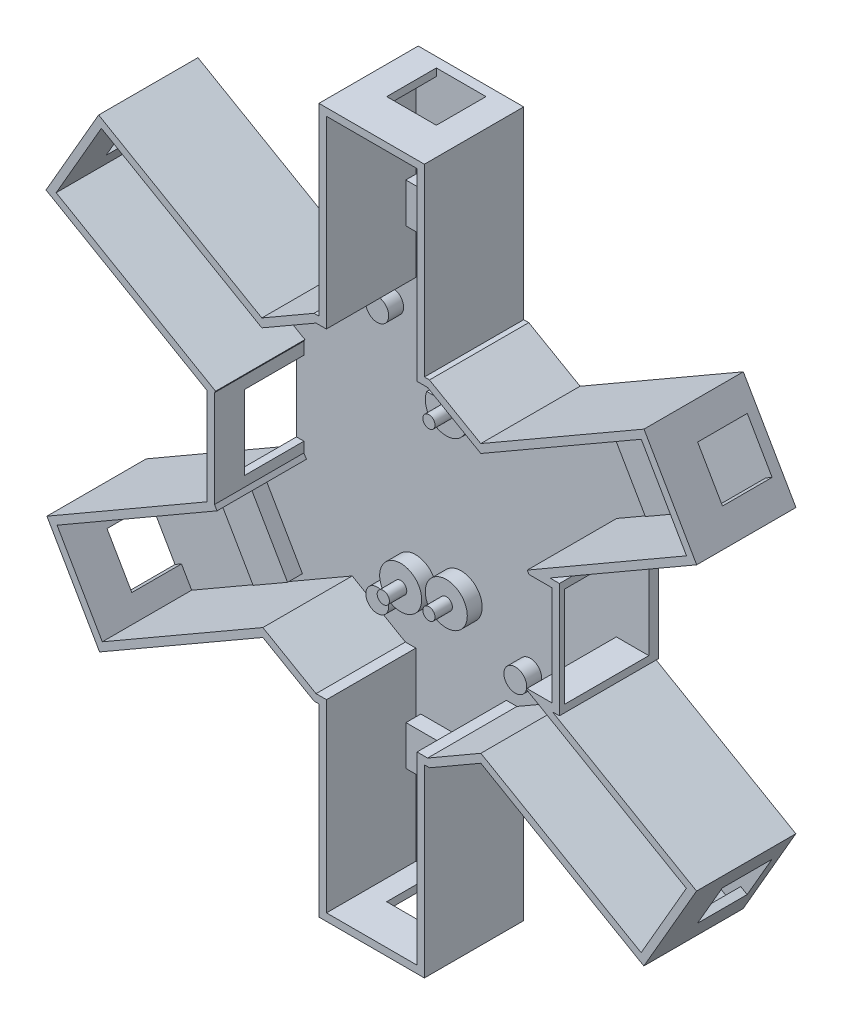
SolidWorks part; units mm, degrees
ref_plane "Ebene vorne" through (0, 0, 0) normal (0, 0, 1) x (1, 0, 0)
ref_plane "Ebene oben" through (0, 0, 0) normal (0, 1, 0) x (1, 0, 0)
ref_plane "Ebene rechts" through (0, 0, 0) normal (1, 0, 0) x (0, 0, -1)
sketch "Skizze1" plane through (0, 0, 0) normal (0, 0, 1) x (1, 0, 0)
  line L0 (-22.15, 25.11) -> (-11.02, 31.53) construction
  line L1 (-11.02, 31.53) -> (-8.35, 31.53) construction
  line L2 (-8.35, 31.53) -> (-8.35, 68.65) construction
  line L3 (-8.35, 68.65) -> (8.29, 68.65) construction
  line L4 (8.29, 68.65) -> (8.29, 31.53) construction
  line L5 (8.29, 31.53) -> (11, 31.53) construction
  line L6 (11, 31.53) -> (21.95, 25.25) construction
  line L7 (21.95, 25.25) -> (53.98, 43.72) construction
  line L8 (53.98, 43.72) -> (62.29, 29.33) construction
  line L9 (-62.48, 29.19) -> (-54.18, 43.59) construction
  line L10 (-54.18, 43.59) -> (-22.15, 25.11) construction
  line L11 (-30.38, 10.62) -> (-62.48, 29.19) construction
  line L12 (-30.88, 9.75) -> (-30.38, 10.62) construction
  line L13 (-30.88, -9.32) -> (-30.88, 9.75) construction
  line L14 (-30.05, -10.67) -> (-30.88, -9.32) construction
  line L15 (-62.3, -29.3) -> (-30.05, -10.67) construction
  line L16 (-53.99, -43.7) -> (-62.3, -29.3) construction
  line L17 (-21.73, -25.09) -> (-53.99, -43.7) construction
  line L18 (-21.52, -25.46) -> (-21.73, -25.09) construction
  line L19 (-11.02, -31.51) -> (-21.52, -25.46) construction
  line L20 (-8.33, -31.51) -> (-11.02, -31.51) construction
  line L21 (-8.33, -68.7) -> (-8.33, -31.51) construction
  line L22 (8.29, -68.7) -> (-8.33, -68.7) construction
  line L23 (8.31, -31.51) -> (8.29, -68.7) construction
  line L24 (11.02, -31.51) -> (8.31, -31.51) construction
  line L25 (21.5, -25.46) -> (11.02, -31.51) construction
  line L26 (21.73, -25.06) -> (21.5, -25.46) construction
  line L27 (53.95, -43.66) -> (21.73, -25.06) construction
  line L28 (62.26, -29.27) -> (53.95, -43.66) construction
  line L29 (30.04, -10.67) -> (62.26, -29.27) construction
  line L30 (30.79, -9.37) -> (30.04, -10.67) construction
  line L31 (35.49, -9.37) -> (30.79, -9.37) construction
  line L32 (35.49, 9.12) -> (35.49, -9.37) construction
  line L33 (31.19, 9.12) -> (35.49, 9.12) construction
  line L34 (30.22, 10.81) -> (31.19, 9.12) construction
  line L35 (62.29, 29.33) -> (30.22, 10.81) construction
  line L36 (-22.15, 25.11) -> (-11.02, 31.53) construction
  line L37 (-11.02, 31.53) -> (-8.35, 31.53) construction
  line L38 (-8.35, 31.53) -> (-8.35, 68.65) construction
  line L39 (-8.35, 68.65) -> (8.29, 68.65) construction
  line L40 (8.29, 68.65) -> (8.29, 31.53) construction
  line L41 (8.29, 31.53) -> (11, 31.53) construction
  line L42 (11, 31.53) -> (21.95, 25.25) construction
  line L43 (21.95, 25.25) -> (53.98, 43.72) construction
  line L44 (53.98, 43.72) -> (62.29, 29.33) construction
  line L45 (-62.48, 29.19) -> (-54.18, 43.59) construction
  line L46 (-54.18, 43.59) -> (-22.15, 25.11) construction
  line L47 (-30.38, 10.62) -> (-62.48, 29.19) construction
  line L48 (-30.88, 9.75) -> (-30.38, 10.62) construction
  line L49 (-30.88, -9.32) -> (-30.88, 9.75) construction
  line L50 (-30.05, -10.67) -> (-30.88, -9.32) construction
  line L51 (-62.3, -29.3) -> (-30.05, -10.67) construction
  line L52 (-53.99, -43.7) -> (-62.3, -29.3) construction
  line L53 (-21.73, -25.09) -> (-53.99, -43.7) construction
  line L54 (-21.52, -25.46) -> (-21.73, -25.09) construction
  line L55 (-11.02, -31.51) -> (-21.52, -25.46) construction
  line L56 (-8.33, -31.51) -> (-11.02, -31.51) construction
  line L57 (-8.33, -68.7) -> (-8.33, -31.51) construction
  line L58 (8.29, -68.7) -> (-8.33, -68.7) construction
  line L59 (8.31, -31.51) -> (8.29, -68.7) construction
  line L60 (11.02, -31.51) -> (8.31, -31.51) construction
  line L61 (21.5, -25.46) -> (11.02, -31.51) construction
  line L62 (21.73, -25.06) -> (21.5, -25.46) construction
  line L63 (53.95, -43.66) -> (21.73, -25.06) construction
  line L64 (62.26, -29.27) -> (53.95, -43.66) construction
  line L65 (30.04, -10.67) -> (62.26, -29.27) construction
  line L66 (30.79, -9.37) -> (30.04, -10.67) construction
  line L67 (35.49, -9.37) -> (30.79, -9.37) construction
  line L68 (35.49, 9.12) -> (35.49, -9.37) construction
  line L69 (31.19, 9.12) -> (35.49, 9.12) construction
  line L70 (30.22, 10.81) -> (31.19, 9.12) construction
  line L71 (62.29, 29.33) -> (30.22, 10.81) construction
  line L72 (-22.15, 26.0336) -> (-11.2342, 32.33)
  line L73 (-11.2342, 32.33) -> (-9.15, 32.33)
  line L74 (-9.15, 32.33) -> (-9.15, 69.45)
  line L75 (-9.15, 69.45) -> (9.09, 69.45)
  line L76 (9.09, 69.45) -> (9.09, 32.33)
  line L77 (9.09, 32.33) -> (11.2131, 32.33)
  line L78 (11.2131, 32.33) -> (21.9489, 26.1729)
  line L79 (21.9489, 26.1729) -> (54.273, 44.8124)
  line L80 (54.273, 44.8124) -> (63.3828, 29.0373)
  line L81 (63.3828, 29.0373) -> (31.311, 10.5162)
  line L82 (31.311, 10.5162) -> (31.6532, 9.92)
  line L83 (31.6532, 9.92) -> (36.29, 9.92)
  line L84 (36.29, 9.92) -> (36.29, -10.17)
  line L85 (36.29, -10.17) -> (31.2521, -10.17)
  line L86 (31.2521, -10.17) -> (31.1326, -10.377)
  line L87 (31.1326, -10.377) -> (63.3529, -28.9772)
  line L88 (63.3529, -28.9772) -> (54.2428, -44.7527)
  line L89 (54.2428, -44.7527) -> (21.9615, -26.1173)
  line L90 (21.9615, -26.1173) -> (21.9615, -26.1173)
  line L91 (21.9615, -26.1173) -> (11.2343, -32.31)
  line L92 (11.2343, -32.31) -> (9.1096, -32.31)
  line L93 (9.1096, -32.31) -> (9.0896, -69.5)
  line L94 (9.0896, -69.5) -> (-9.13, -69.5)
  line L95 (-9.13, -69.5) -> (-9.13, -32.31)
  line L96 (-9.13, -32.31) -> (-11.234, -32.31)
  line L97 (-11.234, -32.31) -> (-21.9457, -26.138)
  line L98 (-21.9457, -26.138) -> (-21.9457, -26.138)
  line L99 (-21.9457, -26.138) -> (-54.2831, -44.7927)
  line L100 (-54.2831, -44.7927) -> (-63.3926, -29.0073)
  line L101 (-63.3926, -29.0073) -> (-31.1621, -10.3886)
  line L102 (-31.1621, -10.3886) -> (-31.68, -9.5463)
  line L103 (-31.68, -9.5463) -> (-31.68, 9.9635)
  line L104 (-31.68, 9.9635) -> (-31.4711, 10.327)
  line L105 (-31.4711, 10.327) -> (-63.572, 28.8975)
  line L106 (-63.572, 28.8975) -> (-54.4734, 44.6829)
  line L107 (-54.4734, 44.6829) -> (-22.15, 26.0336)
  line L108 (-22.1499, 27.7653) -> (-11.6358, 33.83)
  line L109 (-11.6358, 33.83) -> (-10.65, 33.83)
  line L110 (-10.65, 33.83) -> (-10.65, 70.95)
  line L111 (-10.65, 70.95) -> (10.59, 70.95)
  line L112 (10.59, 70.95) -> (10.59, 33.83)
  line L113 (10.59, 33.83) -> (11.6127, 33.83)
  line L114 (11.6127, 33.83) -> (21.9469, 27.9032)
  line L115 (21.9469, 27.9032) -> (54.8223, 46.8607)
  line L116 (54.8223, 46.8607) -> (65.4319, 28.4885)
  line L117 (65.4319, 28.4885) -> (35.8755, 11.42)
  line L118 (35.8755, 11.42) -> (35.8755, 11.42)
  line L119 (35.8755, 11.42) -> (37.79, 11.42)
  line L120 (37.79, 11.42) -> (37.79, -11.67)
  line L121 (37.79, -11.67) -> (36.3727, -11.67)
  line L122 (36.3727, -11.67) -> (36.3727, -11.67)
  line L123 (36.3727, -11.67) -> (65.4021, -28.4282)
  line L124 (65.4021, -28.4282) -> (54.7917, -46.8016)
  line L125 (54.7917, -46.8016) -> (21.9615, -27.8493)
  line L126 (21.9615, -27.8493) -> (21.9615, -27.8493)
  line L127 (21.9615, -27.8493) -> (11.6362, -33.81)
  line L128 (11.6362, -33.81) -> (10.6088, -33.81)
  line L129 (10.6088, -33.81) -> (10.5888, -71)
  line L130 (10.5888, -71) -> (-10.63, -71)
  line L131 (-10.63, -71) -> (-10.63, -33.81)
  line L132 (-10.63, -33.81) -> (-11.6352, -33.81)
  line L133 (-11.6352, -33.81) -> (-21.9453, -27.8694)
  line L134 (-21.9453, -27.8694) -> (-21.9453, -27.8694)
  line L135 (-21.9453, -27.8694) -> (-54.8327, -46.8414)
  line L136 (-54.8327, -46.8414) -> (-65.4412, -28.4584)
  line L137 (-65.4412, -28.4584) -> (-33.18, -9.8219)
  line L138 (-33.18, -9.8219) -> (-33.18, -9.8219)
  line L139 (-33.18, -9.8219) -> (-33.18, 9.5827)
  line L140 (-33.18, 9.5827) -> (-33.18, 9.5827)
  line L141 (-33.18, 9.5827) -> (-65.6194, 28.349)
  line L142 (-65.6194, 28.349) -> (-55.0236, 46.7321)
  line L143 (-55.0236, 46.7321) -> (-22.1499, 27.7653)
  dimension "D1" = 0.8
  dimension "D2" = 1.5
extrude "Aufsatz-Linear austragen1" add sketch "Skizze1" along normal blind 18
sketch "Skizze3" plane through (0, 0, 0) normal (0, 0, -1) x (-1, 0, 0)
  line L31 (55.0236, 46.7321) -> (22.1499, 27.7653)
  line L32 (22.1499, 27.7653) -> (11.6358, 33.83)
  line L33 (11.6358, 33.83) -> (10.65, 33.83)
  line L34 (10.65, 33.83) -> (10.65, 70.95)
  line L35 (10.65, 70.95) -> (-10.59, 70.95)
  line L36 (-10.59, 70.95) -> (-10.59, 33.83)
  line L37 (-10.59, 33.83) -> (-11.6127, 33.83)
  line L38 (-11.6127, 33.83) -> (-21.9469, 27.9032)
  line L39 (-21.9469, 27.9032) -> (-54.8223, 46.8607)
  line L40 (-54.8223, 46.8607) -> (-65.4319, 28.4885)
  line L41 (-65.4319, 28.4885) -> (-35.8755, 11.42)
  line L42 (-35.8755, 11.42) -> (-37.79, 11.42)
  line L43 (-37.79, 11.42) -> (-37.79, -11.67)
  line L44 (-37.79, -11.67) -> (-36.3727, -11.67)
  line L45 (-36.3727, -11.67) -> (-65.4021, -28.4282)
  line L46 (-65.4021, -28.4282) -> (-54.7917, -46.8016)
  line L47 (-54.7917, -46.8016) -> (-21.9615, -27.8493)
  line L48 (-21.9615, -27.8493) -> (-11.6362, -33.81)
  line L49 (-11.6362, -33.81) -> (-10.6088, -33.81)
  line L50 (-10.6088, -33.81) -> (-10.5888, -71)
  line L51 (-10.5888, -71) -> (10.63, -71)
  line L52 (10.63, -71) -> (10.63, -33.81)
  line L53 (10.63, -33.81) -> (11.6352, -33.81)
  line L54 (11.6352, -33.81) -> (21.9453, -27.8694)
  line L55 (21.9453, -27.8694) -> (54.8327, -46.8414)
  line L56 (54.8327, -46.8414) -> (65.4412, -28.4584)
  line L57 (65.4412, -28.4584) -> (33.18, -9.8219)
  line L59 (33.18, -9.8219) -> (33.18, 9.5827)
  line L60 (33.18, 9.5827) -> (65.6194, 28.349)
  line L61 (65.6194, 28.349) -> (55.0236, 46.7321)
  line L62 (55.0236, 46.7321) -> (22.1499, 27.7653)
  line L63 (22.1499, 27.7653) -> (11.6358, 33.83)
  line L64 (11.6358, 33.83) -> (10.65, 33.83)
  line L65 (10.65, 33.83) -> (10.65, 70.95)
  line L66 (10.65, 70.95) -> (-10.59, 70.95)
  line L67 (-10.59, 70.95) -> (-10.59, 33.83)
  line L68 (-10.59, 33.83) -> (-11.6127, 33.83)
  line L69 (-11.6127, 33.83) -> (-21.9469, 27.9032)
  line L70 (-21.9469, 27.9032) -> (-54.8223, 46.8607)
  line L71 (-54.8223, 46.8607) -> (-65.4319, 28.4885)
  line L72 (-65.4319, 28.4885) -> (-35.8755, 11.42)
  line L73 (-35.8755, 11.42) -> (-37.79, 11.42)
  line L74 (-37.79, 11.42) -> (-37.79, -11.67)
  line L75 (-37.79, -11.67) -> (-36.3727, -11.67)
  line L76 (-36.3727, -11.67) -> (-65.4021, -28.4282)
  line L77 (-65.4021, -28.4282) -> (-54.7917, -46.8016)
  line L78 (-54.7917, -46.8016) -> (-21.9615, -27.8493)
  line L79 (-21.9615, -27.8493) -> (-11.6362, -33.81)
  line L80 (-11.6362, -33.81) -> (-10.6088, -33.81)
  line L81 (-10.6088, -33.81) -> (-10.5888, -71)
  line L82 (-10.5888, -71) -> (10.63, -71)
  line L83 (10.63, -71) -> (10.63, -33.81)
  line L84 (10.63, -33.81) -> (11.6352, -33.81)
  line L85 (11.6352, -33.81) -> (21.9453, -27.8694)
  line L86 (21.9453, -27.8694) -> (54.8327, -46.8414)
  line L87 (54.8327, -46.8414) -> (65.4412, -28.4584)
  line L88 (65.4412, -28.4584) -> (33.18, -9.8219)
  line L90 (33.18, -9.8219) -> (33.18, 9.5827)
  line L91 (33.18, 9.5827) -> (65.6194, 28.349)
  line L92 (65.6194, 28.349) -> (55.0236, 46.7321)
  dimension "D1" = 0
extrude "Aufsatz-Linear austragen2" add sketch "Skizze3" along normal blind 2
sketch "Skizze4" plane through (36.29, 0, 0) normal (-1, 0, 0) x (0, 0, 1)
  line L0 (17.0038, 9.92) -> (17.0038, -10.17)
  line L1 (0.8513, 9.92) -> (0, 9.92)
  line L2 (17.0038, -10.17) -> (0.8513, -10.17)
  line L3 (17.0038, 9.92) -> (0.8513, 9.92)
  line L4 (0, 9.92) -> (0, -10.17)
  line L5 (0, -10.17) -> (18, -10.17)
  line L6 (18, -10.17) -> (18, 9.92)
  line L7 (18, 9.92) -> (0, 9.92)
  line L8 (0, 9.92) -> (0, -10.17) construction
  line L9 (0, -10.17) -> (18, -10.17) construction
  line L10 (18, -10.17) -> (18, 9.92) construction
  line L11 (18, 9.92) -> (0, 9.92) construction
  line L12 (0, 9.92) -> (0, -10.17)
  line L13 (0, -10.17) -> (0.8513, -10.17)
  dimension "D1" = 0
extrude "Schnitt-Linear austragen1" cut sketch "Skizze4" against normal up to next
sketch "Skizze5" plane through (-31.68, 0, 0) normal (1, 0, 0) x (0, 0, -1)
  line L0 (-12, -7.5) -> (-12, 7.5)
  line L1 (-12, -7.5) -> (0, -7.5)
  line L2 (-12, 7.5) -> (0, 7.5)
  line L3 (0, -7.5) -> (0, 7.5)
  line L4 (-12, -7.5) -> (0, 7.5) construction
  line L5 (-12, 7.5) -> (0, -7.5) construction
  line L6 (0, 9.9635) -> (0, -9.5463) construction
  point P1 (-6, 0)
  dimension "D1" = 15
  dimension "D2" = 12
  dimension "D3" = 0
extrude "Schnitt-Linear austragen2" cut sketch "Skizze5" against normal up to next
sketch "Skizze6" plane through (0, -71, 0) normal (0, -1, 0) x (1, 0, 0)
  line L0 (-9.13, 0) -> (9.0896, 0) construction
  line L1 (5, 10) -> (-5, 10)
  line L2 (5, 10) -> (5, 0)
  line L3 (5, 0) -> (-5, 0)
  line L4 (-5, 10) -> (-5, 0)
  line L5 (5, 10) -> (-5, 0) construction
  line L6 (5, 0) -> (-5, 10) construction
  line L7 (-9.13, 0) -> (9.0896, 0) construction
  point P0 (0, 5)
  dimension "D1" = 10
  dimension "D2" = 10
sketch "Skizze7" plane through (0, 0, 0) normal (0, 0, 1) x (1, 0, 0)
  circle A0 centre (-9.19, -20.27) radius 1.35 construction
  circle A1 centre (0, -18.5) radius 1.35 construction
  circle A2 centre (0, 15) radius 1.35 construction
  circle A3 centre (-9.19, -20.27) radius 4.35
  circle A4 centre (0, -18.5) radius 4.35
  circle A5 centre (0, 15) radius 4.35
  circle A6 centre (0, 15) radius 1.23
  circle A7 centre (0, -18.5) radius 1.23
  circle A8 centre (-9.19, -20.27) radius 1.23
  point P0 (-9.19, -21.62)
  point P1 (-7.84, -20.27)
  point P2 (-9.19, -18.92)
  point P3 (0, -17.15)
  point P5 (-1.35, -18.5)
  point P6 (0, -19.85)
  point P7 (-1.35, 15)
  point P8 (0, 16.35)
  point P13 (1.35, 15)
  dimension "D1" = 3
  dimension "D2" = 0.12
  dimension "D3" = 0.12
  dimension "D4" = 0.12
extrude "Aufsatz-Linear austragen3" add sketch "Skizze7" along normal blind 6.5 contours A6 | A7 | A8
sketch "Skizze8" plane through (0, 0, 0) normal (0, 0, 1) x (1, 0, 0)
  line L0 (3.9365, 16.5483) -> (-3.9365, 16.5483)
  circle A0 centre (-9.19, -20.27) radius 1.23 construction
  circle A1 centre (-9.19, -20.27) radius 1.23 construction
  circle A2 centre (0, -18.5) radius 1.23 construction
  circle A3 centre (0, -18.5) radius 1.23 construction
  circle A4 centre (0, 15) radius 1.23 construction
  circle A5 centre (0, 15) radius 1.23 construction
  circle A6 centre (-9.19, -20.27) radius 4.23
  circle A7 centre (0, -18.5) radius 4.23
  arc A8 (-3.9365, 16.5483) -> (3.9365, 16.5483) centre (0, 15) ccw
  circle A9 centre (0, 15) radius 4.23 construction
  circle A10 centre (13.9, 25.8971) radius 2.3
  circle A11 centre (-13.9, 25.8971) radius 2.3
  circle A12 centre (13.9, -24.8616) radius 2.3
  circle A13 centre (-13.9, -24.8616) radius 2.3
  dimension "D2" = 4.6
  dimension "D3" = 4.6
  dimension "D4" = 4.6
  dimension "D5" = 4.6
  dimension "D6" = 13.9
  dimension "D7" = 13.9
  dimension "D1" = 3
extrude "Aufsatz-Linear austragen4" add sketch "Skizze8" along normal blind 3
sketch "Skizze9" plane through (0, 0, 0) normal (0, 0, 1) x (1, 0, 0)
  line L0 (-9.13, -42.31) -> (-9.13, -52.31) construction
  line L1 (-9.13, -42.31) -> (9.0954, -42.31) construction
  line L2 (-9.13, -52.31) -> (9.0954, -52.31) construction
  line L3 (9.0954, -42.31) -> (9.0954, -52.31) construction
  line L4 (30.622, -31.1169) -> (39.2825, -36.1164) construction
  line L5 (30.622, -31.1169) -> (39.7347, -15.3313) construction
  line L6 (39.2825, -36.1164) -> (48.3952, -20.3309) construction
  line L7 (39.7347, -15.3313) -> (48.3952, -20.3309) construction
  line L8 (39.7303, 15.3783) -> (48.3901, 20.3792) construction
  line L9 (39.7303, 15.3783) -> (30.62, 31.1541) construction
  line L10 (48.3901, 20.3792) -> (39.2797, 36.155) construction
  line L11 (30.62, 31.1541) -> (39.2797, 36.155) construction
  line L12 (9.09, 42.33) -> (9.09, 52.33) construction
  line L13 (9.09, 42.33) -> (-9.1623, 42.33) construction
  line L14 (9.09, 52.33) -> (-9.1623, 52.33) construction
  line L15 (-9.1623, 42.33) -> (-9.1623, 52.33) construction
  line L16 (-39.4734, 36.0285) -> (-30.8117, 31.031) construction
  line L17 (-39.4734, 36.0285) -> (-48.6218, 20.1723) construction
  line L18 (-30.8117, 31.031) -> (-39.9601, 15.1748) construction
  line L19 (-48.6218, 20.1723) -> (-39.9601, 15.1748) construction
  line L20 (-48.3915, -20.3415) -> (-39.7324, -15.3394) construction
  line L21 (-48.3915, -20.3415) -> (-39.2717, -36.1285) construction
  line L22 (-39.7324, -15.3394) -> (-30.6127, -31.1264) construction
  line L23 (-39.2717, -36.1285) -> (-30.6127, -31.1264) construction
  line L24 (-39.107, 34.6626) -> (-47.2559, 20.5387)
  line L25 (-47.2559, 20.5387) -> (-40.3265, 16.5407)
  line L26 (-32.1776, 30.6646) -> (-40.3265, 16.5407)
  line L27 (-39.107, 34.6626) -> (-32.1776, 30.6646)
  line L28 (-8.1623, 43.33) -> (-8.1623, 51.33)
  line L29 (8.09, 51.33) -> (-8.1623, 51.33)
  line L30 (8.09, 43.33) -> (8.09, 51.33)
  line L31 (8.09, 43.33) -> (-8.1623, 43.33)
  line L32 (40.0962, 16.7443) -> (31.9861, 30.7882)
  line L33 (31.9861, 30.7882) -> (38.9139, 34.7889)
  line L34 (47.024, 20.745) -> (38.9139, 34.7889)
  line L35 (40.0962, 16.7443) -> (47.024, 20.745)
  line L36 (40.1008, -16.6973) -> (47.0292, -20.6969)
  line L37 (38.9164, -34.7504) -> (47.0292, -20.6969)
  line L38 (31.988, -30.7508) -> (38.9164, -34.7504)
  line L39 (31.988, -30.7508) -> (40.1008, -16.6973)
  line L40 (8.0954, -43.31) -> (8.0954, -51.31)
  line L41 (-8.13, -51.31) -> (8.0954, -51.31)
  line L42 (-8.13, -43.31) -> (-8.13, -51.31)
  line L43 (-8.13, -43.31) -> (8.0954, -43.31)
  line L44 (-38.906, -34.7624) -> (-31.9788, -30.7607)
  line L45 (-40.0981, -16.7055) -> (-31.9788, -30.7607)
  line L46 (-47.0253, -20.7072) -> (-40.0981, -16.7055)
  line L47 (-47.0253, -20.7072) -> (-38.906, -34.7624)
  line L50 (-11.2342, 32.33) -> (-22.15, 26.0336)
  line L51 (-22.15, 26.0336) -> (-54.4734, 44.6829)
  line L52 (-54.4734, 44.6829) -> (-63.572, 28.8975)
  line L53 (-63.572, 28.8975) -> (-31.4711, 10.327)
  line L54 (-31.4711, 10.327) -> (-31.68, 9.9635)
  line L55 (-31.68, 9.9635) -> (-31.68, 7.5)
  line L56 (-31.68, 7.5) -> (-33.18, 7.5)
  line L57 (-33.18, 7.5) -> (-33.18, -7.5)
  line L58 (-33.18, -7.5) -> (-31.68, -7.5)
  line L59 (-31.68, -7.5) -> (-31.68, -9.5463)
  line L60 (-31.68, -9.5463) -> (-31.1621, -10.3886)
  line L61 (-31.1621, -10.3886) -> (-63.3926, -29.0073)
  line L62 (-63.3926, -29.0073) -> (-54.2831, -44.7927)
  line L63 (-54.2831, -44.7927) -> (-21.9457, -26.138)
  line L64 (-21.9457, -26.138) -> (-11.234, -32.31)
  line L65 (-11.234, -32.31) -> (-9.13, -32.31)
  line L66 (-9.13, -32.31) -> (-9.13, -69.5)
  line L67 (-9.13, -69.5) -> (9.0896, -69.5)
  line L68 (9.0896, -69.5) -> (9.1096, -32.31)
  line L69 (9.1096, -32.31) -> (11.2343, -32.31)
  line L70 (11.2343, -32.31) -> (21.9615, -26.1173)
  line L71 (21.9615, -26.1173) -> (54.2428, -44.7527)
  line L72 (54.2428, -44.7527) -> (63.3529, -28.9772)
  line L73 (63.3529, -28.9772) -> (31.1326, -10.377)
  line L74 (31.1326, -10.377) -> (31.2521, -10.17)
  line L75 (31.2521, -10.17) -> (37.79, -10.17)
  line L76 (37.79, -10.17) -> (37.79, 9.92)
  line L77 (37.79, 9.92) -> (31.6532, 9.92)
  line L78 (31.6532, 9.92) -> (31.311, 10.5162)
  line L79 (31.311, 10.5162) -> (63.3828, 29.0373)
  line L80 (63.3828, 29.0373) -> (54.273, 44.8124)
  line L81 (54.273, 44.8124) -> (21.9489, 26.1729)
  line L82 (21.9489, 26.1729) -> (11.2131, 32.33)
  line L83 (11.2131, 32.33) -> (9.09, 32.33)
  line L84 (9.09, 32.33) -> (9.09, 69.45)
  line L85 (9.09, 69.45) -> (-9.15, 69.45)
  line L86 (-9.15, 69.45) -> (-9.15, 32.33)
  line L87 (-9.15, 32.33) -> (-11.2342, 32.33)
  line L88 (-11.2342, 32.33) -> (-22.15, 26.0336) construction
  line L89 (-22.15, 26.0336) -> (-54.4734, 44.6829) construction
  line L90 (-54.4734, 44.6829) -> (-63.572, 28.8975) construction
  line L91 (-63.572, 28.8975) -> (-31.4711, 10.327) construction
  line L92 (-31.4711, 10.327) -> (-31.68, 9.9635) construction
  line L93 (-31.68, 9.9635) -> (-31.68, 7.5) construction
  line L94 (-31.68, 7.5) -> (-33.18, 7.5) construction
  line L95 (-33.18, 7.5) -> (-33.18, -7.5) construction
  line L96 (-33.18, -7.5) -> (-31.68, -7.5) construction
  line L97 (-31.68, -7.5) -> (-31.68, -9.5463) construction
  line L98 (-31.68, -9.5463) -> (-31.1621, -10.3886) construction
  line L99 (-31.1621, -10.3886) -> (-63.3926, -29.0073) construction
  line L100 (-63.3926, -29.0073) -> (-54.2831, -44.7927) construction
  line L101 (-54.2831, -44.7927) -> (-21.9457, -26.138) construction
  line L102 (-21.9457, -26.138) -> (-11.234, -32.31) construction
  line L103 (-11.234, -32.31) -> (-9.13, -32.31) construction
  line L104 (-9.13, -32.31) -> (-9.13, -69.5) construction
  line L105 (-9.13, -69.5) -> (9.0896, -69.5) construction
  line L106 (9.0896, -69.5) -> (9.1096, -32.31) construction
  line L107 (9.1096, -32.31) -> (11.2343, -32.31) construction
  line L108 (11.2343, -32.31) -> (21.9615, -26.1173) construction
  line L109 (21.9615, -26.1173) -> (54.2428, -44.7527) construction
  line L110 (54.2428, -44.7527) -> (63.3529, -28.9772) construction
  line L111 (63.3529, -28.9772) -> (31.1326, -10.377) construction
  line L112 (31.1326, -10.377) -> (31.2521, -10.17) construction
  line L113 (31.2521, -10.17) -> (37.79, -10.17) construction
  line L114 (37.79, -10.17) -> (37.79, 9.92) construction
  line L115 (37.79, 9.92) -> (31.6532, 9.92) construction
  line L116 (31.6532, 9.92) -> (31.311, 10.5162) construction
  line L117 (31.311, 10.5162) -> (63.3828, 29.0373) construction
  line L118 (63.3828, 29.0373) -> (54.273, 44.8124) construction
  line L119 (54.273, 44.8124) -> (21.9489, 26.1729) construction
  line L120 (21.9489, 26.1729) -> (11.2131, 32.33) construction
  line L121 (11.2131, 32.33) -> (9.09, 32.33) construction
  line L122 (9.09, 32.33) -> (9.09, 69.45) construction
  line L123 (9.09, 69.45) -> (-9.15, 69.45) construction
  line L124 (-9.15, 69.45) -> (-9.15, 32.33) construction
  line L125 (-9.15, 32.33) -> (-11.2342, 32.33) construction
  dimension "D1" = 0
  dimension "D2" = 10
  dimension "D3" = 10
  dimension "D4" = 10
  dimension "D5" = 10
  dimension "D6" = 10
  dimension "D7" = 10
  dimension "D8" = 10
  dimension "D9" = 10
  dimension "D10" = 10
  dimension "D11" = 10
  dimension "D12" = 10
  dimension "D13" = 10
  dimension "D14" = 1
extrude "Aufsatz-Linear austragen7" add sketch "Skizze9" along normal blind 3
sketch "Skizze11" plane through (0, 69.45, 0) normal (0, -1, 0) x (1, 0, 0)
  line L1 (-5, 0) -> (5, 0)
  line L2 (-5, 0) -> (-5, 10)
  line L3 (-5, 10) -> (5, 10)
  line L4 (-9.15, 0) -> (9.09, 0)
  line L5 (9.09, 0) -> (9.09, 18)
  line L6 (9.09, 18) -> (-9.15, 18)
  line L7 (-9.15, 18) -> (-9.15, 0)
  line L8 (-9.15, 0) -> (9.09, 0) construction
  line L9 (9.09, 0) -> (9.09, 18) construction
  line L10 (9.09, 18) -> (-9.15, 18) construction
  line L11 (-9.15, 18) -> (-9.15, 0) construction
  line L12 (5, 0) -> (5, 10)
  dimension "D2" = 5
  dimension "D3" = 10
  dimension "D4" = 10
  dimension "D1" = 0
extrude "Schnitt-Linear austragen3" cut sketch "Skizze11" against normal up to next
sketch "Skizze12" plane through (-60.2212, 34.7108, 0) normal (0.8664, -0.4994, 0) x (0, 0, -1)
  line L4 (0, -6.7099) -> (0, 11.51)
  line L5 (0, 11.51) -> (-18, 11.51)
  line L6 (-18, 11.51) -> (-18, -6.7099)
  line L7 (-18, -6.7099) -> (0, -6.7099)
  line L8 (0, -6.7099) -> (0, 11.51) construction
  line L9 (0, 11.51) -> (-18, 11.51) construction
  line L10 (-18, 11.51) -> (-18, -6.7099) construction
  line L11 (-18, -6.7099) -> (0, -6.7099) construction
  dimension "D1" = 0
ref_axis "Achse1" through (0, 0, -3) along (0, 0, 1)
sketch "Skizze13" plane through (60.1066, 34.7106, 0) normal (-0.866, -0.5001, 0) x (0, 0, 1)
  line L0 (0, -6.5514) -> (0, 11.6652) construction
  line L1 (0, -6.5514) -> (0, 11.6652) construction
  line L2 (0, 7.5569) -> (0, -2.4431)
  line L3 (0, 7.5569) -> (10, 7.5569)
  line L4 (0, -2.4431) -> (10, -2.4431)
  line L5 (10, 7.5569) -> (10, -2.4431)
  point P2 (0, 2.5569)
  point P5 (0, 2.5569)
  dimension "D1" = 10
  dimension "D2" = 10
extrude "Schnitt-Linear austragen4" cut sketch "Skizze13" against normal up to next
sketch "Skizze14" plane through (60.0581, -34.6826, 0) normal (-0.866, 0.5001, 0) x (0, 0, 1)
  line L0 (0, -11.6286) -> (0, 6.5885) construction
  line L1 (0, -11.6286) -> (0, 6.5885) construction
  line L2 (0, 2.4799) -> (0, -7.5201)
  line L3 (0, 2.4799) -> (10, 2.4799)
  line L4 (0, -7.5201) -> (10, -7.5201)
  line L5 (10, 2.4799) -> (10, -7.5201)
  point P2 (0, -2.5201)
  point P3 (0, -2.5201)
  dimension "D1" = 10
  dimension "D2" = 10
extrude "Schnitt-Linear austragen5" cut sketch "Skizze14" against normal up to next
sketch "Skizze15" plane through (0, -69.5, 0) normal (0, 1, 0) x (1, 0, 0)
  line L0 (-9.13, 0) -> (9.0896, 0) construction
  line L1 (-9.13, 0) -> (9.0896, 0) construction
  line L2 (-5.0202, 0) -> (4.9798, 0)
  line L3 (-5.0202, 0) -> (-5.0202, -10)
  line L4 (4.9798, 0) -> (4.9798, -10)
  line L5 (-5.0202, -10) -> (4.9798, -10)
  point P2 (-0.0202, 0)
  point P3 (-0.0202, 0)
  dimension "D1" = 10
  dimension "D2" = 10
extrude "Schnitt-Linear austragen6" cut sketch "Skizze15" against normal up to next
sketch "Skizze16" plane through (-60.113, -34.6902, 0) normal (0.8661, 0.4998, 0) x (0, 0, -1)
  line L0 (0, 6.5614) -> (0, -11.6639) construction
  line L1 (0, 6.5614) -> (0, -11.6639) construction
  line L2 (0, 2.4487) -> (0, -7.5513)
  line L3 (0, 2.4487) -> (-10, 2.4487)
  line L4 (0, -7.5513) -> (-10, -7.5513)
  line L5 (-10, 2.4487) -> (-10, -7.5513)
  point P2 (0, -2.5513)
  point P3 (0, -2.5513)
  dimension "D1" = 10
  dimension "D2" = 10
extrude "Schnitt-Linear austragen7" cut sketch "Skizze16" against normal up to next
sketch "Skizze17" plane through (-60.2212, 34.7108, 0) normal (0.8664, -0.4994, 0) x (0, 0, -1)
  line L0 (0, 11.51) -> (0, -6.7099) construction
  line L1 (0, 11.51) -> (0, -6.7099) construction
  line L2 (0, 7.4) -> (0, -2.6)
  line L3 (0, 7.4) -> (-10, 7.4)
  line L4 (0, -2.6) -> (-10, -2.6)
  line L5 (-10, 7.4) -> (-10, -2.6)
  point P2 (0, 2.4)
  point P3 (0, 2.4)
  dimension "D1" = 10
  dimension "D2" = 10
extrude "Schnitt-Linear austragen8" cut sketch "Skizze17" against normal up to next
